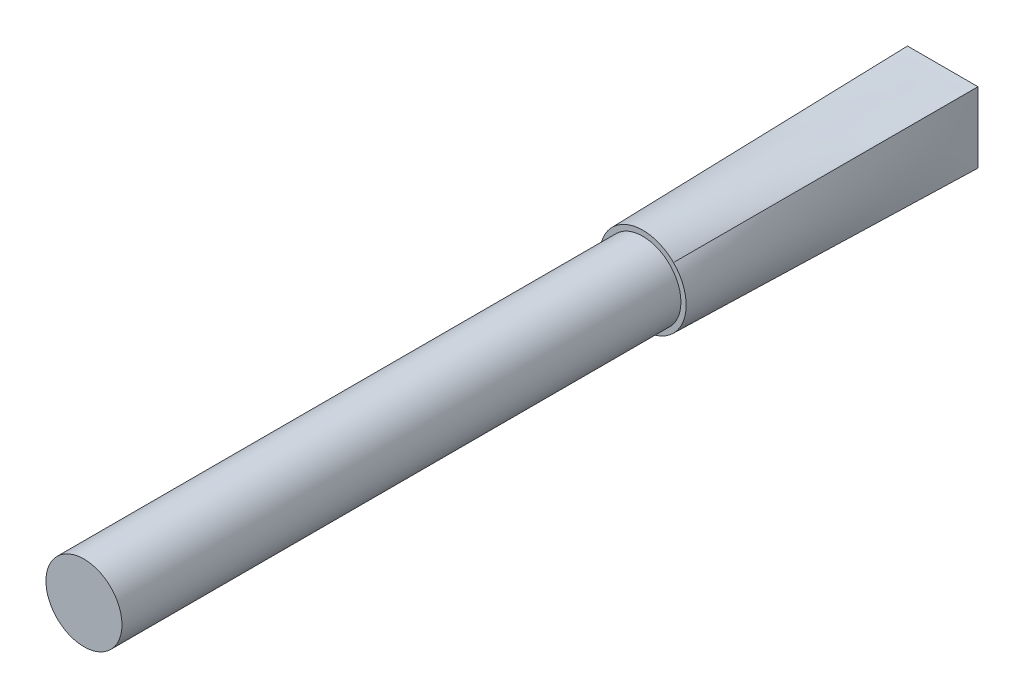
SolidWorks part; units mm, degrees
ref_plane "Front Plane" through (0, 0, 0) normal (0, 0, 1) x (1, 0, 0)
ref_plane "Top Plane" through (0, 0, 0) normal (0, 1, 0) x (1, 0, 0)
ref_plane "Right Plane" through (0, 0, 0) normal (1, 0, 0) x (0, 0, -1)
sketch "Sketch1" plane through (0, 0, 0) normal (0, 0, 1) x (1, 0, 0)
  circle A0 centre (-46.9561, 36.6858) radius 6.15 construction
  circle A1 centre (-46.9561, 36.6858) radius 6.15
extrude "Boss-Extrude1" add sketch "Sketch1" along normal blind 17
extrude "Boss-Extrude2" add sketch "Sketch1<2>" against normal blind 73.4
sketch "Sketch1<2>" plane through (0, 0, 0) normal (0, 0, 1) x (1, 0, 0) same geometry as "Sketch1"
sketch "Sketch2" plane through (0, 0, -73.4) normal (0, 0, -1) x (-1, 0, 0)
  circle A0 centre (46.9561, 36.6858) radius 7
  dimension "D1" = 14
ref_plane "Plane1" through (0, 0, -121.9) normal (0, 0, -1) x (-1, 0, 0)
sketch "Sketch3" plane through (0, 0, -121.9) normal (0, 0, -1) x (-1, 0, 0)
  line L1 (41.2561, 42.3858) -> (52.6561, 42.3858)
  line L2 (41.2561, 42.3858) -> (41.2561, 30.9858)
  line L3 (41.2561, 30.9858) -> (52.6561, 30.9858)
  line L4 (52.6561, 42.3858) -> (52.6561, 30.9858)
  line L5 (41.2561, 42.3858) -> (52.6561, 30.9858) construction
  line L6 (41.2561, 30.9858) -> (52.6561, 42.3858) construction
  circle A0 centre (46.9561, 36.6858) radius 6.15 construction
  dimension "D1" = 11.4
loft "Loft1" add profiles "Sketch3", "Sketch2" connector at (-41.2561, 42.3858, -121.9) connector at (-41.8473, 41.4712, -73.4)
sketch "Sketch4" plane through (0, 0, -121.9) normal (0, 0, -1) x (-1, 0, 0)
  line L1 (42.1061, 31.8358) -> (51.8061, 31.8358)
  line L2 (42.1061, 31.8358) -> (42.1061, 41.5358)
  line L3 (42.1061, 41.5358) -> (51.8061, 41.5358)
  line L4 (51.8061, 31.8358) -> (51.8061, 41.5358)
  line L5 (42.1061, 31.8358) -> (51.8061, 41.5358) construction
  line L6 (42.1061, 41.5358) -> (51.8061, 31.8358) construction
  point P0 (46.9561, 36.6858)
  dimension "D1" = 9.7
extrude "Cut-Extrude1" cut sketch "Sketch4" against normal blind 1.5
fillet "Fillet1" radius 1 4 edges at (-51.8061, 41.5358, -121.15) (-51.8061, 31.8358, -121.15) (-42.1061, 41.5358, -121.15) (-42.1061, 31.8358, -121.15)
